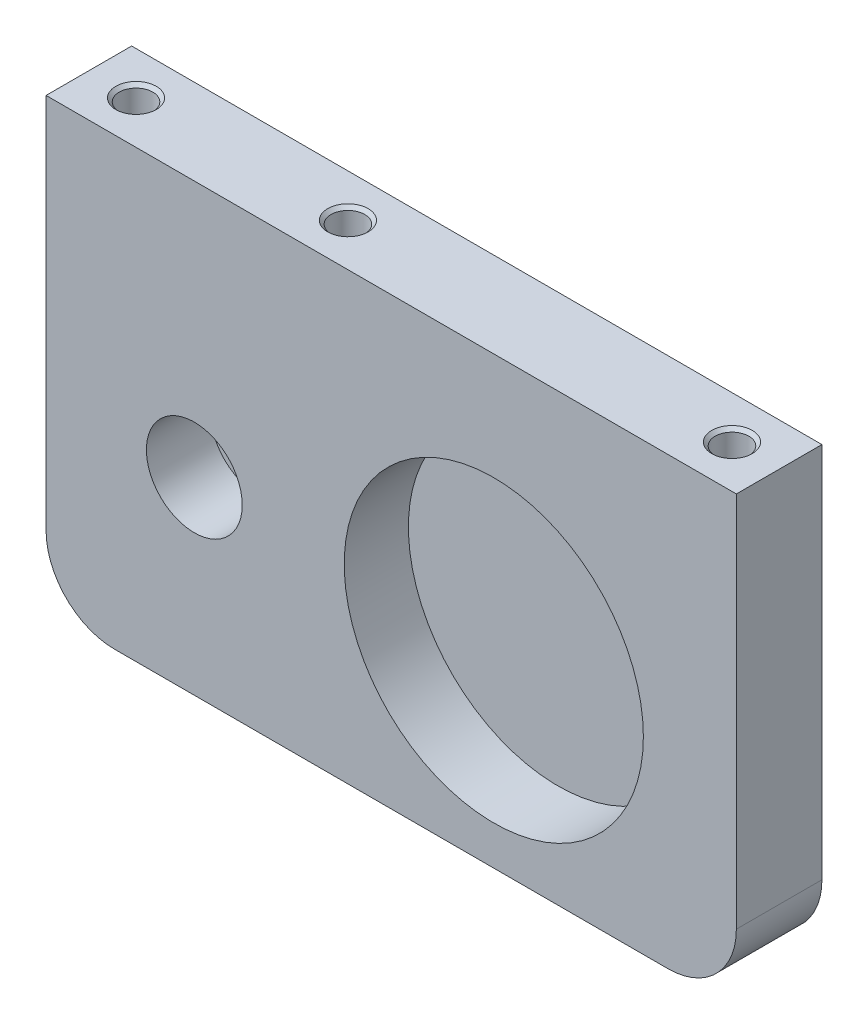
SolidWorks part; units mm, degrees
ref_plane "Front Plane" through (0, 0, 0) normal (0, 0, 1) x (1, 0, 0)
ref_plane "Top Plane" through (0, 0, 0) normal (0, 1, 0) x (1, 0, 0)
ref_plane "Right Plane" through (0, 0, 0) normal (1, 0, 0) x (0, 0, -1)
sketch "Sketch1" plane through (0, 0, 0) normal (0, 0, 1) x (1, 0, 0)
  line L10 (-33.225, 19.05) -> (18, 19.05)
  line L11 (-33.225, 19.05) -> (-33.225, -14)
  line L12 (-33.225, -14) -> (18, -14)
  line L13 (18, 19.05) -> (18, -14)
  circle A2 centre (0, 0) radius 11.1 construction
  circle A3 centre (-22.225, 0) radius 3.556 construction
  dimension "D2" = 7.112
  dimension "D5" = 19.05
  dimension "D6" = 11
  dimension "D3" = 22.225
  dimension "D1" = 22.2
  dimension "D8" = 51.225
  dimension "D4" = 14
  dimension "D7" = 18
extrude "Boss-Extrude1" add sketch "Sketch1" against normal blind 6.35
sketch "Sketch8" plane through (0, 19.05, 0) normal (0, 1, 0) x (1, 0, 0)
  line L0 (-33.225, 3.175) -> (18, 3.175) construction
  line L1 (-33.225, 6.35) -> (-33.225, 0) construction
  line L2 (18, 6.35) -> (18, 0) construction
  circle A1 centre (-29.725, 3.175) radius 1.25
  circle A2 centre (-14, 3.175) radius 1.25
  circle A3 centre (14.5, 3.175) radius 1.25
  dimension "D1" = 2.5
  dimension "D2" = 3.5
  dimension "D3" = 3.5
  dimension "D4" = 14
extrude "Cut-Extrude4" cut sketch "Sketch8" against normal blind 15
sketch "Sketch10" plane through (0, 0, 0) normal (0, 0, 1) x (1, 0, 0)
  circle A0 centre (-22.225, 0) radius 3.556 construction
  circle A1 centre (0, 0) radius 11.1 construction
  circle A2 centre (-22.225, 0) radius 3.556
  circle A3 centre (0, 0) radius 11.1
extrude "Cut-Extrude5" cut sketch "Sketch10" against normal offset from surface (4.7625 mm away) 1.5875 up to face at (-7.6125, 2.525, -6.35)
fillet "Fillet3" radius 5.08 2 edges at (18, -14, -3.175) (-33.225, -14, -3.175)
chamfer "Chamfer1" distance 0.25 angle 45 3 edges at (14.5, 19.05, -1.925) (-14, 19.05, -1.925) (-29.725, 19.05, -1.925)
